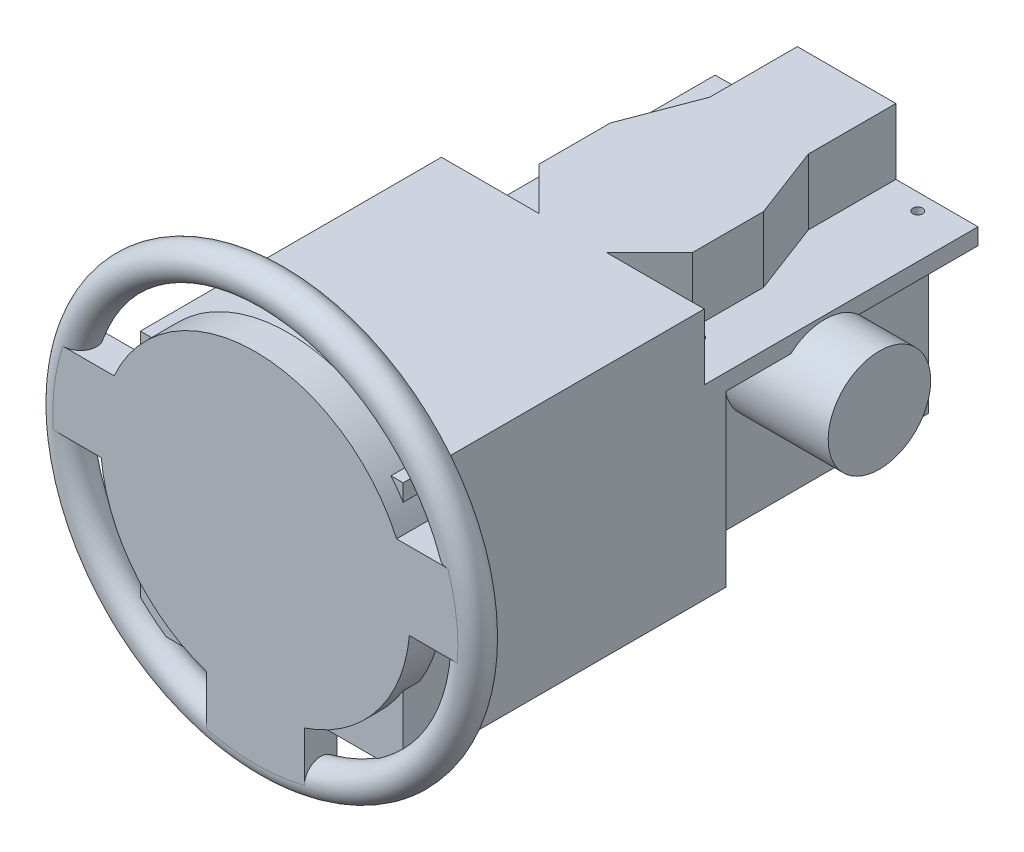
SolidWorks part; units mm, degrees
ref_plane "Płaszczyzna przednia" through (0, 0, 0) normal (0, 0, 1) x (1, 0, 0)
ref_plane "Płaszczyzna górna" through (0, 0, 0) normal (0, 1, 0) x (1, 0, 0)
ref_plane "Płaszczyzna prawa" through (0, 0, 0) normal (1, 0, 0) x (0, 0, -1)
sketch "Szkic4" plane through (0, 0, 0) normal (0, 1, 0) x (1, 0, 0)
  line L0 (0, 0) -> (0, -14.1713) construction
  line L1 (0, 0) -> (-185, 0) construction
  circle A0 centre (-185, 0) radius 15
  dimension "D1" = 30
  dimension "D2" = 185
revolve "Obrót2" add sketch "Szkic4" angle 360 about L0
sketch "Szkic5" plane through (0, 0, 0) normal (0, 0, 1) x (1, 0, 0)
  line L0 (0, 141.2771) -> (0, -223.1934) construction
  line L1 (-175.7848, 57.6603) -> (-128.9748, 57.6603)
  line L2 (-184.5472, -12.936) -> (-140.6836, -12.936)
  line L3 (-44.7738, -133.9945) -> (-44.7738, -179.5002)
  line L4 (44.7738, -133.9945) -> (44.7738, -179.5002)
  line L5 (128.9748, 57.6603) -> (175.7848, 57.6603)
  line L6 (140.6836, -12.936) -> (184.5472, -12.936)
  line L7 (-170, 0) -> (-200, 0) construction
  arc A0 (-140.6836, -12.936) -> (-44.7738, -133.9945) centre (0, 0) ccw
  arc A1 (-175.7848, 57.6603) -> (-184.5472, -12.936) centre (0, 0) ccw
  arc A2 (44.7738, -133.9945) -> (140.6836, -12.936) centre (0, 0) ccw
  arc A3 (128.9748, 57.6603) -> (-128.9748, 57.6603) centre (0, 0) ccw
  arc A4 (-44.7738, -179.5002) -> (44.7738, -179.5002) centre (0, 0) ccw
  arc A5 (184.5472, -12.936) -> (175.7848, 57.6603) centre (0, 0) ccw
  circle A6 centre (0, 0) radius 170 construction
  circle A7 centre (0, 0) radius 200 construction
  circle A8 centre (0, 0) radius 185 construction
  point P23 (-185, 0)
extrude "Dodanie-wyciągnięcie1" add sketch "Szkic5" against normal blind 15 and the other way blind 15 separate body contours L3 A4 L4 A2 L6 A5 L5 A3 L1 A1 L2 A0
sketch "Szkic6" plane through (0, 0, 0) normal (0, 1, 0) x (1, 0, 0)
  line L0 (0, -15) -> (0, 525) construction
  line L3 (-185, -15) -> (185, -15) construction
  dimension "D1" = 540
sketch "Szkic7" plane through (0, 0, 0) normal (0, 0, 1) x (1, 0, 0)
  line L0 (120, 90) -> (-120, -140) construction
  line L1 (120, 90) -> (-120, 90)
  line L2 (120, 90) -> (120, -140)
  line L3 (120, -140) -> (-120, -140)
  line L4 (-120, 90) -> (-120, -140)
  line L5 (-120, 90) -> (120, -140) construction
  line L6 (0, -140) -> (0, 0) construction
  dimension "D1" = 240
  dimension "D2" = 230
  dimension "D3" = 140
extrude "Dodanie-wyciągnięcie2" add sketch "Szkic7" against normal up to vertex (525 mm away) up to point (0, 0, -525)
sketch "Szkic8" plane through (0, 0, 0) normal (0, 1, 0) x (1, 0, 0)
  line L0 (0, -15) -> (0, 485)
  line L1 (0, -15) -> (0, 525) construction
  dimension "D1" = 500
sketch "Szkic9" plane through (0, 0, -525) normal (0, 0, -1) x (-1, 0, 0)
  line L0 (120, -74.5601) -> (120, 74.5601) construction
  line L1 (-120, 90) -> (120, 90)
  line L2 (-120, 90) -> (-120, 30)
  line L3 (-120, 30) -> (120, 30)
  line L4 (120, 90) -> (120, 30)
  line L6 (-70, 30) -> (70, 30)
  line L7 (-70, 30) -> (-70, 90)
  line L8 (-70, 90) -> (70, 90)
  line L9 (70, 30) -> (70, 90)
  point P11 (0, 90)
  point P12 (0, 90)
  line M5 (-120, 90) -> (-120, -140)
  line M7 (120, -140) -> (120, 90)
  line M8 (120, 90) -> (-120, 90)
  dimension "D1" = 60
  dimension "D2" = 140
extrude "Wytnij-wyciągnięcie1" cut sketch "Szkic9" against normal blind 250 contours L3 L7 L1 M5 | L9 L3 M7 M8 region at (95, 60, -525) region at (-95, 60, -525)
sketch "Szkic10" plane through (0, 0, -525) normal (0, 0, -1) x (-1, 0, 0)
  line L0 (120, -140) -> (-120, -140) construction
  line L1 (-75, -140) -> (75, -140)
  line L2 (-75, -140) -> (-75, 15)
  line L3 (-75, 15) -> (75, 15)
  line L4 (75, -140) -> (75, 15)
  line L5 (120, 30) -> (120, -140) construction
  line L6 (-120, -140) -> (120, -140)
  line L7 (-120, -140) -> (-120, 15)
  line L8 (-120, 15) -> (120, 15)
  line L9 (120, -140) -> (120, 15)
  line L10 (-120, 30) -> (-70, 30) construction
  point P13 (0, 15)
  point P14 (0, 15)
  line M10 (-120, 30) -> (-120, -140)
  line M11 (-120, -140) -> (120, -140)
  line M12 (120, -140) -> (120, 30)
  dimension "D1" = 150
  dimension "D2" = 15
extrude "Wytnij-wyciągnięcie2" cut sketch "Szkic10" against normal blind 230 contours L8 L4 M11 M12 | L8 L2 M10 M11 region at (97.5, -62.5, -525) region at (-97.5, -62.5, -525)
sketch "Szkic11" plane through (0, 30, 0) normal (0, 1, 0) x (1, 0, 0)
  line L0 (120, 525) -> (70, 525) construction
  line L1 (0, -15) -> (0, 525) construction
  circle A0 centre (80, 510) radius 4.5
  circle A1 centre (80, 310) radius 4.5
  circle A2 centre (-80, 310) radius 4.5
  circle A3 centre (-80, 510) radius 4.5
  dimension "D1" = 9
  dimension "D2" = 160
  dimension "D3" = 160
  dimension "D4" = 200
  dimension "D5" = 15
  dimension "D6" = 80
extrude "Wytnij-wyciągnięcie3" cut sketch "Szkic11" against normal blind 230
sketch "Szkic12" plane through (0, 0, -525) normal (0, 0, -1) x (-1, 0, 0)
  line L0 (75, -140) -> (75, 15) construction
  line L1 (-75, 15) -> (75, 15)
  line L2 (-75, 15) -> (-75, -25)
  line L3 (-75, -25) -> (75, -25)
  line L4 (75, 15) -> (75, -25)
  line L6 (-45, 15) -> (45, 15)
  line L7 (-45, 15) -> (-45, -25)
  line L8 (-45, -25) -> (45, -25)
  line L9 (45, 15) -> (45, -25)
  point P11 (0, -25)
  point P12 (0, -25)
  line M9 (75, -140) -> (75, 15)
  line M15 (-75, 15) -> (-75, -140)
  dimension "D1" = 90
  dimension "D2" = 40
extrude "Wytnij-wyciągnięcie4" cut sketch "Szkic12" against normal up to surface (230 mm away) contours L7 L1 L3 M15 | L1 L9 L3 M9 region at (60, -5, -525) region at (-60, -5, -525) up to face at (97.5, -62.5, -295)
sketch "Szkic13" plane through (120, 0, 0) normal (1, 0, 0) x (0, 0, -1)
  line L0 (525, -140) -> (525, -25) construction
  line L1 (275, 90) -> (0, 90) construction
  circle A0 centre (385, -20) radius 46.8123
  dimension "D1" = 140
  dimension "D2" = 110
extrude "Dodanie-wyciągnięcie3" add sketch "Szkic13" against normal up to surface (75 mm away) and the other way blind 50 up to face at (45, -5, -410)
sketch "Szkic14" plane through (0, 90, 0) normal (0, 1, 0) x (1, 0, 0)
  line L0 (70, 314.1421) -> (30.8579, 275)
  line L1 (70, 275) -> (70, 525) construction
  line L2 (30.8579, 275) -> (-30.8579, 275)
  line L3 (120, 275) -> (70, 275) construction
  line L4 (0, -15) -> (0, 525) construction
  line L5 (70, 379.1421) -> (45, 445)
  line L6 (70, 275) -> (70, 525) construction
  line L8 (70, 314.1421) -> (70, 379.1421)
  line L9 (45, 445) -> (45, 525)
  line L10 (70, 525) -> (-70, 525) construction
  line L11 (45, 525) -> (-45, 525)
  line L12 (0, -220) -> (0, 220) construction
  line L13 (-45, 445) -> (-45, 525)
  line L14 (-70, 379.1421) -> (-45, 445)
  line L15 (-70, 314.1421) -> (-70, 379.1421)
  line L16 (-70, 314.1421) -> (-30.8579, 275)
  line L18 (70, 275) -> (-70, 275)
  line L19 (70, 275) -> (70, 525)
  line L20 (70, 525) -> (-70, 525)
  line L21 (-70, 275) -> (-70, 525)
  circle A1 centre (80, 310) radius 4.5 construction
  point P23 (0, 525)
  point P27 (0, 275)
  line M11 (70, 275) -> (70, 525)
  line M12 (70, 525) -> (-70, 525)
  line M13 (-70, 525) -> (-70, 275)
  dimension "D1" = 10
  dimension "D2" = 45
  dimension "D3" = 80
  dimension "D4" = 45
  dimension "D5" = 65
extrude "Wytnij-wyciągnięcie5" cut sketch "Szkic14" against normal up to surface (60 mm away) contours L18 L0 M11 | L18 L16 M13 | L14 L13 M13 M12 | L9 L5 M11 M12 region at (56.9526, 90, -288.0474) region at (58.715, 90, -466.9352) region at (-56.9526, 90, -288.0474) region at (-58.715, 90, -466.9352) up to face at (80, 30, -305.5)
